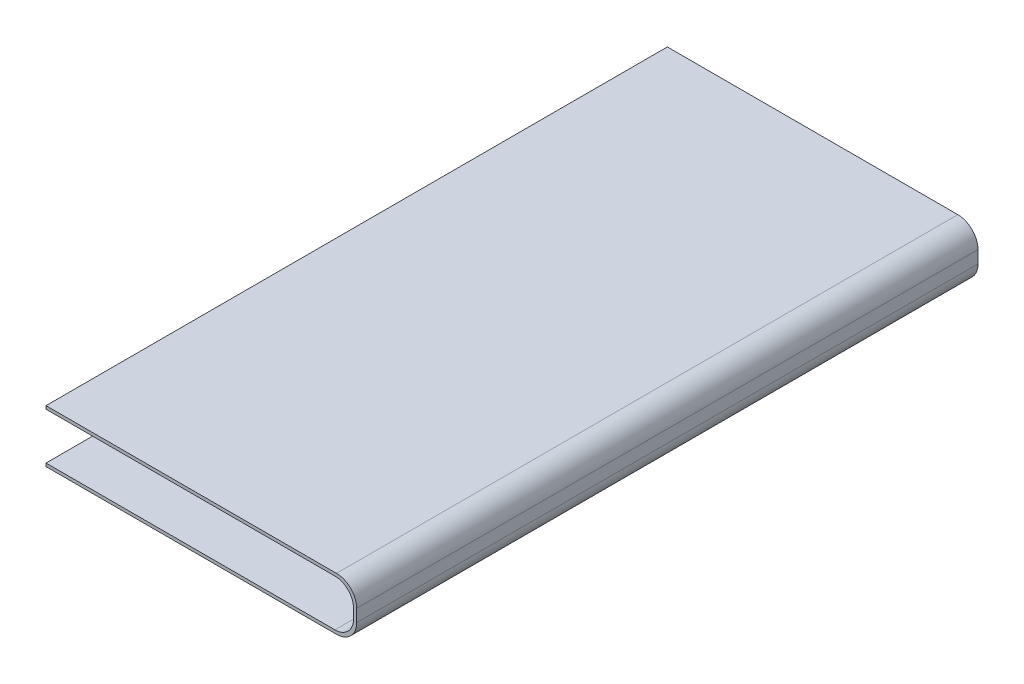
SolidWorks part; units mm, degrees
ref_plane "Спереди" through (0, 0, 0) normal (0, 0, 1) x (1, 0, 0)
ref_plane "Сверху" through (0, 0, 0) normal (0, 1, 0) x (1, 0, 0)
ref_plane "Справа" through (0, 0, 0) normal (1, 0, 0) x (0, 0, -1)
sketch "Эскиз1" plane through (0, 0, 0) normal (0, 0, 1) x (1, 0, 0)
  line L0 (14.5, -1.65) -> (23.85, -1.65)
  line L1 (-27, -1.65) -> (27, -1.65) construction
  line L2 (24.5, -2.3) -> (24.5, -2.7)
  line L3 (23.85, -3.35) -> (14.5, -3.35)
  line L4 (14.5, -1.75) -> (23.8, -1.75)
  line L5 (24.4, -2.35) -> (24.4, -2.65)
  line L6 (23.8, -3.25) -> (14.5, -3.25)
  line L7 (14.5, -1.65) -> (14.5, -1.75)
  line L8 (14.5, -3.25) -> (14.5, -3.35)
  line L9 (24, -4.05) -> (24, -1.65) construction
  line L10 (24.5, -1.65) -> (24.5, -3.35) construction
  line L11 (24.5, -3.35) -> (14.5, -3.35) construction
  line L12 (14.5, -1.65) -> (24.5, -1.65) construction
  line L13 (24.4, -1.75) -> (24.4, -3.25) construction
  line L14 (24.4, -3.25) -> (14.5, -3.25) construction
  line L15 (14.5, -1.75) -> (24.4, -1.75) construction
  arc A0 (24.5, -2.7) -> (23.85, -3.35) centre (23.85, -2.7) cw
  arc A1 (23.85, -1.65) -> (24.5, -2.3) centre (23.85, -2.3) cw
  arc A2 (24.4, -2.65) -> (23.8, -3.25) centre (23.8, -2.65) cw
  arc A3 (23.8, -1.75) -> (24.4, -2.35) centre (23.8, -2.35) cw
  point P15 (24.5, -3.35)
  dimension "D5" = 0.65
  dimension "D6" = 0.6
  dimension "D2" = 0.5
  dimension "D3" = 1.7
  dimension "D4" = 10
  dimension "D1" = 0.1
extrude "Бобышка-Вытянуть1" add sketch "Эскиз1" along normal mid plane 20
